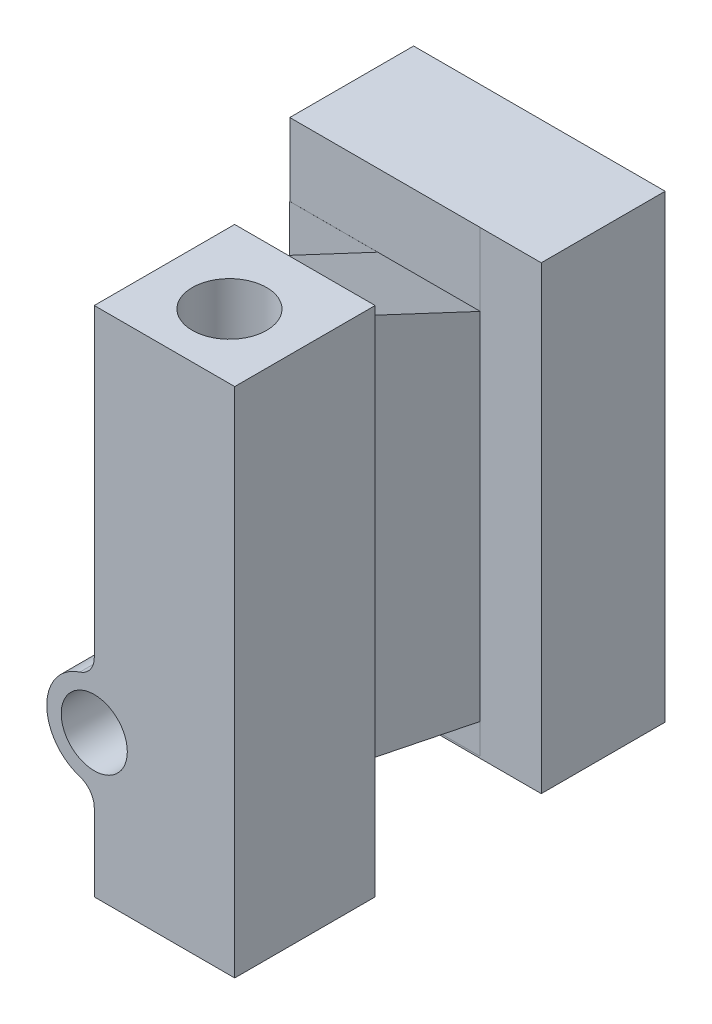
SolidWorks part; units mm, degrees
ref_plane "Front Plane" through (0, 0, 0) normal (0, 0, 1) x (1, 0, 0)
ref_plane "Top Plane" through (0, 0, 0) normal (0, 1, 0) x (1, 0, 0)
ref_plane "Right Plane" through (0, 0, 0) normal (1, 0, 0) x (0, 0, -1)
sketch "Sketch1" plane through (0, 0, 0) normal (0, 0, 1) x (1, 0, 0)
  line L1 (-22.1812, 49.3094) -> (11.8188, 49.3094)
  line L2 (-22.1812, 49.3094) -> (-22.1812, -74.6906)
  line L3 (-22.1812, -74.6906) -> (11.8188, -74.6906)
  line L4 (11.8188, 49.3094) -> (11.8188, -74.6906)
  dimension "D1" = 124
  dimension "D2" = 34
extrude "Boss-Extrude1" add sketch "Sketch1" along normal blind 34
sketch "Sketch2" plane through (0, 0, 34) normal (0, 0, 1) x (1, 0, 0)
  line L0 (-22.1812, 49.3094) -> (-22.1812, -74.6906) construction
  circle A0 centre (-22.1812, -40.2508) radius 11.504
extrude "Boss-Extrude2" add sketch "Sketch2" against normal blind 34
fillet "Fillet1" radius 5 2 edges at (-22.1812, -51.7548, 17) (-22.1812, -28.7468, 17)
sketch "Sketch3" plane through (0, -74.6906, 0) normal (0, -1, 0) x (1, 0, 0)
  circle A0 centre (-4.8936, 17.1062) radius 13.5862
extrude "Cut-Extrude1" cut sketch "Sketch3" against normal blind 50
sketch "Sketch4" plane through (0, 0, 34) normal (0, 0, 1) x (1, 0, 0)
  circle A0 centre (-22.1812, -40.2508) radius 8
  arc A1 (-25.6665, -29.2874) -> (-25.6665, -51.2142) centre (-22.1812, -40.2508) ccw construction
extrude "Cut-Extrude2" cut sketch "Sketch4" against normal blind 20
sketch "Sketch5" plane through (0, 0, 0) normal (0, 0, -1) x (-1, 0, 0)
  line L1 (-7.2618, 48.6909) -> (17.5691, 48.6909)
  line L2 (-7.2618, 48.6909) -> (-7.2618, -62.513)
  line L3 (-7.2618, -62.513) -> (17.5691, -62.513)
  line L4 (17.5691, 48.6909) -> (17.5691, -62.513)
extrude "Boss-Extrude3" add sketch "Sketch5" along normal blind 30
sketch "Sketch6" plane through (0, 0, -30) normal (0, 0, -1) x (-1, 0, 0)
  line L1 (-22.0319, 48.3699) -> (38.868, 48.3699)
  line L2 (-22.0319, 48.3699) -> (-22.0319, -62.9411)
  line L3 (-22.0319, -62.9411) -> (38.868, -62.9411)
  line L4 (38.868, 48.3699) -> (38.868, -62.9411)
extrude "Boss-Extrude4" add sketch "Sketch6" along normal blind 30
sketch "Sketch7" plane through (0, 49.3094, 0) normal (0, 1, 0) x (1, 0, 0)
  circle A0 centre (-5.0915, -18.3589) radius 8.9987
extrude "Cut-Extrude3" cut sketch "Sketch7" against normal blind 100
sketch "Sketch9" plane through (7.2618, 0, 0) normal (1, 0, 0) x (0, 0, -1)
  line L0 (-0.0119, 53.1584) -> (-0.0119, 44.8625)
  line L1 (-0.0119, 44.8625) -> (30.0187, 30.7835)
  line L2 (30.0187, 30.7835) -> (30.0187, 53.1584)
  line L3 (30.0187, 53.1584) -> (-0.0119, 53.1584)
  line L4 (-0.0119, -49.0284) -> (-0.0119, -66.3738)
  line L5 (-0.0119, -66.3738) -> (29.9948, -69.2814)
  line L6 (29.9948, -69.2814) -> (29.9948, -55.1732)
  line L7 (29.9948, -55.1732) -> (-0.0119, -49.0284)
extrude "Cut-Extrude5" cut sketch "Sketch9" against normal blind 100
sketch "Sketch10" plane through (-38.868, 0, 0) normal (-1, 0, 0) x (0, 0, 1)
  line L0 (-60, -62.9411) -> (-60, 48.3699) construction
  line L1 (-60, -62.9411) -> (-30, -62.9411) construction
  circle A0 centre (-45, -22.9411) radius 8.0865
  point P2 (0, 0)
  point P3 (-45.0158, -24.249)
  dimension "D1" = 15
  dimension "D2" = 40
extrude "Cut-Extrude6" cut sketch "Sketch10" against normal blind 10
